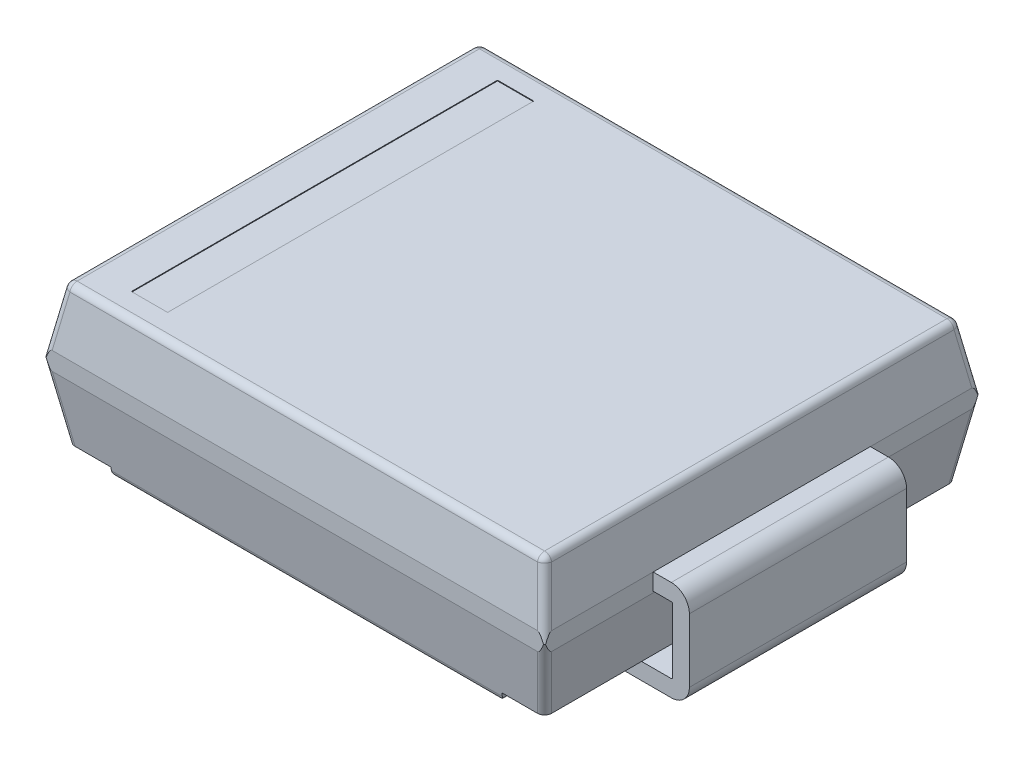
SolidWorks part; units mm, degrees
ref_plane "Front Plane" through (0, 0, 0) normal (0, 0, 1) x (1, 0, 0)
ref_plane "Top Plane" through (0, 0, 0) normal (0, 1, 0) x (1, 0, 0)
ref_plane "Right Plane" through (0, 0, 0) normal (1, 0, 0) x (0, 0, -1)
sketch "Sketch5" plane through (0, 0, 0) normal (0, 0, 1) x (1, 0, 0)
  line L0 (-3.45, 0.2524) -> (-3.45, 0.0024)
  line L1 (-3.45, 0.2524) -> (-3.3125, 1.0324)
  line L2 (3.45, 0.2524) -> (3.45, 0.0024)
  line L3 (0, 0) -> (-0.663, 0) construction
  line L4 (-3.45, 0.0024) -> (-3.2916, -0.896)
  line L5 (3.45, 0.0024) -> (3.2916, -0.896)
  line L6 (3.45, 0.2524) -> (3.3125, 1.0324)
  line L7 (3.45, 0.2524) -> (3.45, 0.0024)
  line L8 (0, 0) -> (0, 0.4546) construction
  line L9 (-3.45, 0.0024) -> (-1.6581, 0.0024) construction
  line L10 (3.3125, 1.0324) -> (-3.3125, 1.0324)
  line L11 (-3.2916, -0.896) -> (-2.7, -0.896)
  line L12 (2.7, -1.0276) -> (-2.7, -1.0276)
  line L13 (-3.45, 0.2524) -> (-3.45, 0.0024)
  line L14 (-2.7, -0.896) -> (-2.7, -1.0276)
  line L15 (2.7, -0.896) -> (2.7, -1.0276)
  line L16 (3.2916, -0.896) -> (2.7, -0.896)
  line L17 (-0.6495, -1.1276) -> (-0.7495, -1.1276) construction
  dimension "D1" = 0.75
  dimension "D2" = 0.1315
  dimension "D3" = 0.25
  dimension "D4" = 10
  dimension "D5" = 10
  dimension "BodyLength" = 6.9
  dimension "D6" = 10
  dimension "D7" = 10
  dimension "Height" = 2.16
  dimension "A1" = 0.1
extrude "Extrude2" add sketch "Sketch5" along normal mid plane 6 contours L12 L5 L2 L6 L10 L1 L0 L4 region at (0, 0.0165, 0)
sketch "Sketch15" plane through (0, 0, 0) normal (1, 0, 0) x (0, 0, -1)
  line L0 (2.6684, -1.878) -> (3, 0.0024)
  line L1 (3, 0.0024) -> (3, 0.2524)
  line L2 (3, 0.2524) -> (2.6064, 2.4845)
  dimension "D1" = 10
  dimension "D2" = 10
extrude "Extrude10" cut sketch "Sketch15" against normal through all and the other way through all flip side to cut
mirror "Mirror1" about plane through (0, 0, 0) normal (0, 0, 1) of "Extrude10"
sketch "Sketch9" plane through (0, 0, 0) normal (0, 0, 1) x (1, 0, 0)
  line L0 (-3.45, 0.2524) -> (-3.7, 0.2524)
  line L1 (-3.95, 0.0024) -> (-3.95, -0.8776)
  line L2 (-3.7, -1.1276) -> (-2.8, -1.1276)
  line L3 (-3.45, 0.0224) -> (-3.7, 0.0224)
  line L4 (-3.72, 0.0024) -> (-3.72, -0.8776)
  line L5 (-3.7, -0.8976) -> (-2.8, -0.8976)
  line L6 (-2.8, -0.8976) -> (-2.8, -1.1276)
  line L7 (-3.45, 0.2524) -> (-3.45, 0.0224)
  line L8 (0, 0) -> (0, -0.4455) construction
  line L9 (3.45, 0.2524) -> (3.45, 0.0224)
  line L10 (2.8, -0.8976) -> (2.8, -1.1276)
  line L11 (3.7, -0.8976) -> (2.8, -0.8976)
  line L12 (3.72, 0.0024) -> (3.72, -0.8776)
  line L13 (3.45, 0.0224) -> (3.7, 0.0224)
  line L14 (3.7, -1.1276) -> (2.8, -1.1276)
  line L15 (3.95, 0.0024) -> (3.95, -0.8776)
  line L16 (3.45, 0.2524) -> (3.7, 0.2524)
  arc A0 (-3.7, 0.2524) -> (-3.95, 0.0024) centre (-3.7, 0.0024) ccw
  arc A1 (-3.95, -0.8776) -> (-3.7, -1.1276) centre (-3.7, -0.8776) ccw
  arc A2 (-3.7, 0.0224) -> (-3.72, 0.0024) centre (-3.7, 0.0024) ccw
  arc A3 (-3.72, -0.8776) -> (-3.7, -0.8976) centre (-3.7, -0.8776) ccw
  arc A4 (3.72, -0.8776) -> (3.7, -0.8976) centre (3.7, -0.8776) cw
  arc A5 (3.7, 0.0224) -> (3.72, 0.0024) centre (3.7, 0.0024) cw
  arc A6 (3.95, -0.8776) -> (3.7, -1.1276) centre (3.7, -0.8776) cw
  arc A7 (3.7, 0.2524) -> (3.95, 0.0024) centre (3.7, 0.0024) cw
  dimension "D1" = 0.25
  dimension "TotalLength" = 7.9
  dimension "PinLength" = 1.15
  dimension "C" = 0.23
extrude "Extrude6" add sketch "Sketch9" along normal mid plane 3
fillet "Fillet1" radius 0.1 16 edges at (0, -1.0276, -2.8184) (-2.7, -1.0276, 0) (0, -1.0276, 2.8184) (2.7, -1.0276, 0) (-3.3125, 1.0324, 0) (0, 1.0324, -2.8625) (3.3125, 1.0324, 0) (0, 1.0324, 2.8625) (-3.3708, -0.4468, -2.9208) (-3.3812, 0.6424, -2.9312) (-3.3812, 0.6424, 2.9312) (-3.3708, -0.4468, 2.9208) (3.3708, -0.4468, 2.9208) (3.3812, 0.6424, 2.9312) (3.3708, -0.4468, -2.9208) (3.3812, 0.6424, -2.9312)
sketch "Sketch17" plane through (0, 1.0324, 0) normal (0, 1, 0) x (1, 0, 0)
  line L0 (-3.2286, 2.7786) -> (-3.2286, -2.7786) construction
  line L1 (-2.7286, 2.5286) -> (-2.2286, 2.5286)
  line L2 (-2.7286, 2.5286) -> (-2.7286, -2.5286)
  line L3 (-2.7286, -2.5286) -> (-2.2286, -2.5286)
  line L4 (-2.2286, 2.5286) -> (-2.2286, -2.5286)
  line L5 (3.2286, 2.7786) -> (-3.2286, 2.7786) construction
  line L6 (0, 0) -> (-0.2283, 0) construction
  dimension "D1" = 0.5
  dimension "D2" = 0.5
  dimension "D3" = 0.25
extrude "Extrude11" cut sketch "Sketch17" against normal blind 0.01
